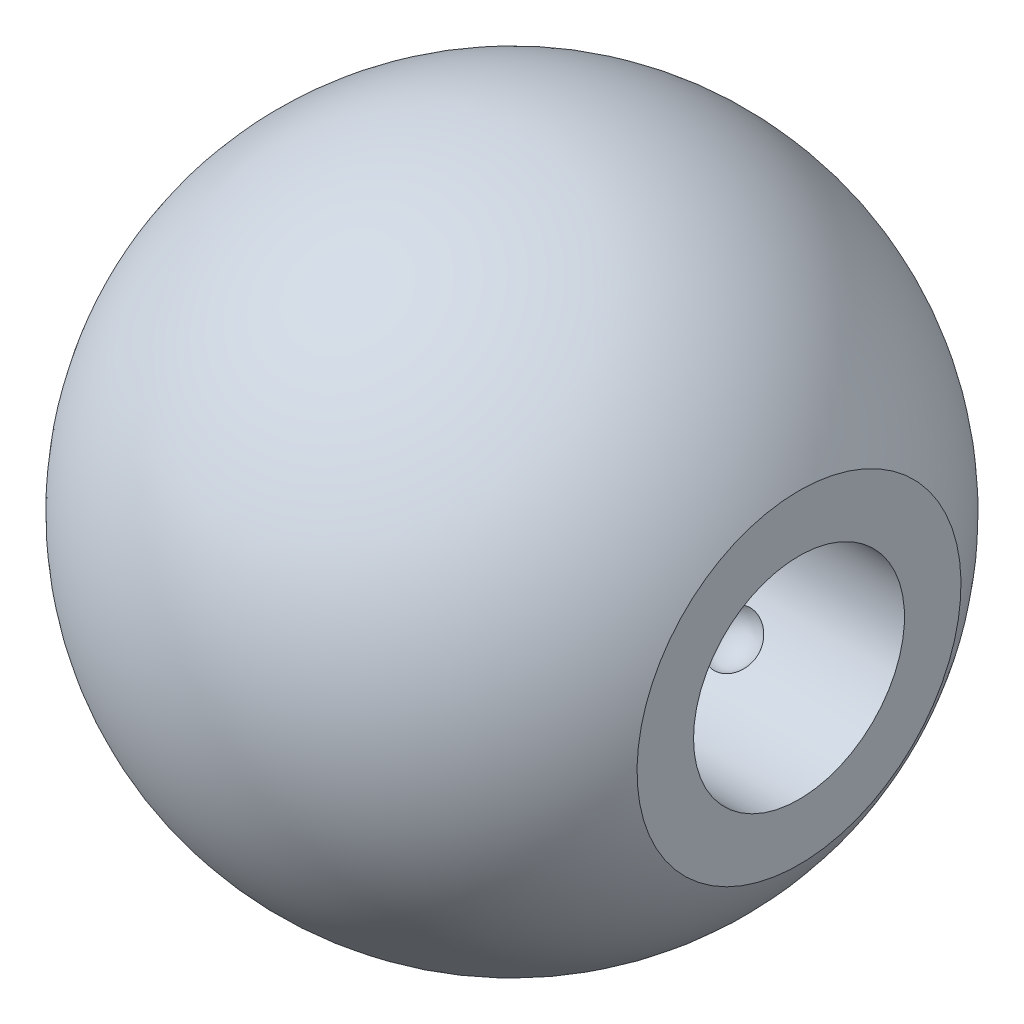
SolidWorks part; units mm, degrees
ref_plane "Front Plane" through (0, 0, 0) normal (0, 0, 1) x (1, 0, 0)
ref_plane "Top Plane" through (0, 0, 0) normal (0, 1, 0) x (1, 0, 0)
ref_plane "Right Plane" through (0, 0, 0) normal (1, 0, 0) x (0, 0, -1)
sketch "Sketch1" plane through (0, 0, 0) normal (1, 0, 0) x (0, 0, -1)
  circle A0 centre (0, 0) radius 11.2
  circle A1 centre (0, 0) radius 13.5
  dimension "D1" = 22.4
  dimension "D2" = 27
extrude "Boss-Extrude1" add sketch "Sketch1" along normal blind 60
sketch "Sketch2" plane through (0, 0, 0) normal (0, 0, 1) x (1, 0, 0)
  line L0 (8, 12.6) -> (8, 9.6)
  line L1 (8, 9.6) -> (11, 9.6)
  line L2 (0, 13.5) -> (0, -13.5) construction
  arc A0 (8, 12.6) -> (11, 9.6) centre (8, 9.6) cw
  dimension "D1" = 3
  dimension "D2" = 12.6
  dimension "D3" = 8
revolve "Cut-Revolve1" cut sketch "Sketch2" angle 360 about L0
pattern_circular "CirPattern1" count 8 over 360 about axis through (60, 0, 0) along (-1, 0, 0) of "Cut-Revolve1" reverse direction yes
pattern_linear "LPattern1" count 3 spacing 20 along (1, 0, 0) of "CirPattern1"
fillet "Fillet1" radius 3 1 edges at (0, 0, -11.2)
sketch "Sketch3" plane through (0, 0, 0) normal (0, 0, 1) x (1, 0, 0)
  line L0 (0, 0) -> (123.7677, 0) construction
  line L1 (0, 13.5) -> (60, 13.5)
  line L2 (60, 13.5) -> (60, 11.2)
  line L4 (60, 11.2) -> (62.7738, 11.2)
  line L5 (62.7738, 11.2) -> (62.7738, 17.2)
  arc A0 (0, 13.5) -> (62.7738, 17.2) centre (32.2916, 0) cw
  dimension "D1" = 35
  dimension "D2" = 6
revolve "Revolve1" add sketch "Sketch3" angle 360 about L0
